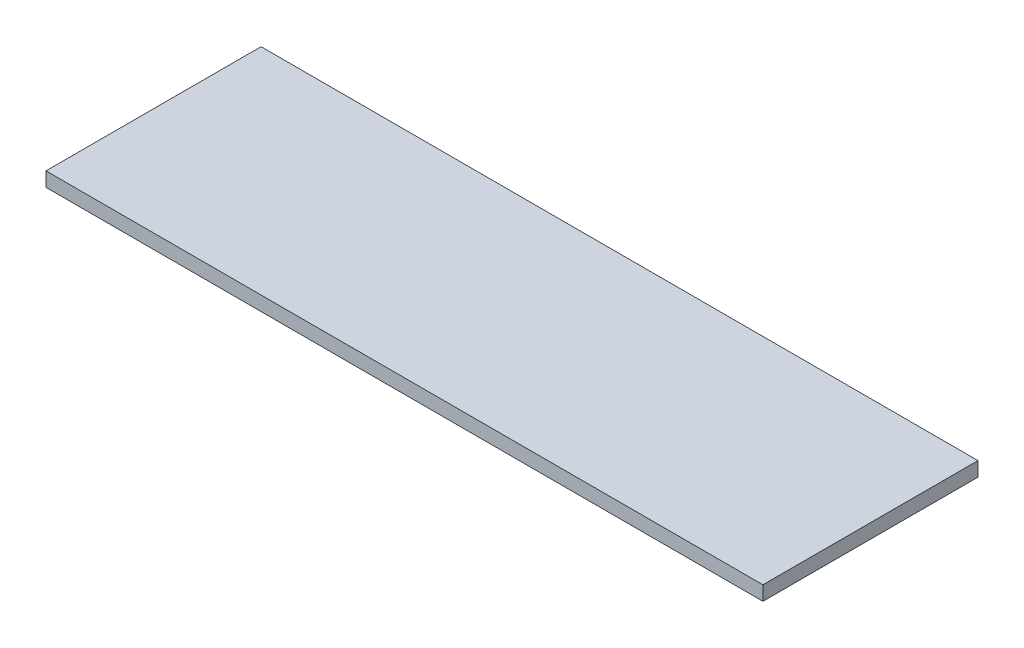
SolidWorks part; units mm, degrees
ref_plane "Front Plane" through (0, 0, 0) normal (0, 0, 1) x (1, 0, 0)
ref_plane "Top Plane" through (0, 0, 0) normal (0, 1, 0) x (1, 0, 0)
ref_plane "Right Plane" through (0, 0, 0) normal (1, 0, 0) x (0, 0, -1)
sketch "Sketch1" plane through (0, 0, 0) normal (0, 1, 0) x (1, 0, 0)
  line L1 (-75, 22.5) -> (75, 22.5)
  line L2 (-75, 22.5) -> (-75, -22.5)
  line L3 (-75, -22.5) -> (75, -22.5)
  line L4 (75, 22.5) -> (75, -22.5)
  line L5 (-75, 22.5) -> (75, -22.5) construction
  line L6 (-75, -22.5) -> (75, 22.5) construction
  point P0 (0, 0)
  dimension "D1" = 45
  dimension "D2" = 150
extrude "Boss-Extrude1" add sketch "Sketch1" along normal blind 3
